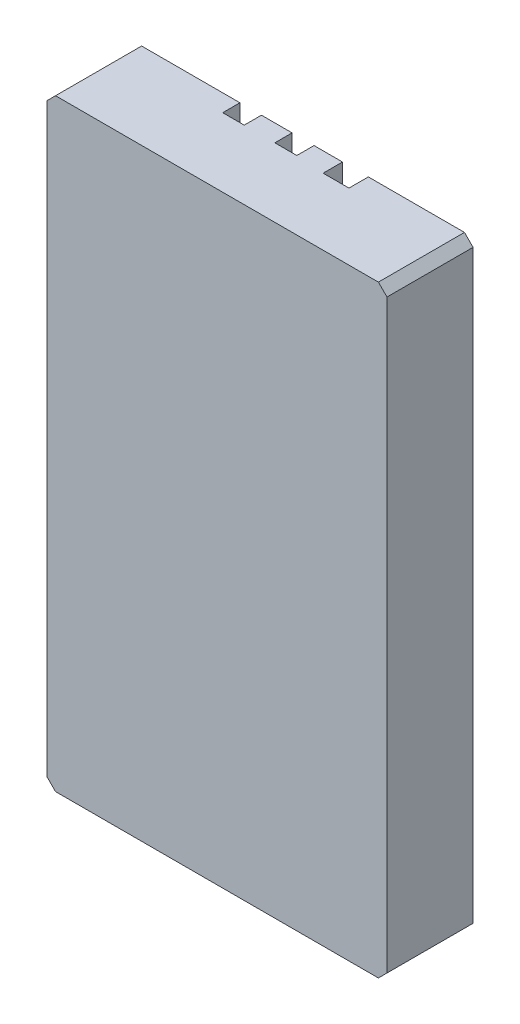
SolidWorks part; units mm, degrees
ref_plane "Front Plane" through (0, 0, 0) normal (0, 0, 1) x (1, 0, 0)
ref_plane "Top Plane" through (0, 0, 0) normal (0, 1, 0) x (1, 0, 0)
ref_plane "Right Plane" through (0, 0, 0) normal (1, 0, 0) x (0, 0, -1)
sketch "Sketch1" plane through (0, 0, 0) normal (0, 0, 1) x (1, 0, 0)
  line L0 (-59.5, -49) -> (17.5, -49) construction
  line L1 (-60.5, -59) -> (18.5, -59)
  line L2 (-60.5, -59) -> (-60.5, -199)
  line L3 (-60.5, -199) -> (18.5, -199)
  line L4 (18.5, -59) -> (18.5, -199)
  dimension "D1" = 79
  dimension "D2" = 140
  dimension "D3" = 10
extrude "Boss-Extrude1" add sketch "Sketch1" against normal blind 20
sketch "Sketch3" plane through (0, -59, 0) normal (0, 1, 0) x (1, 0, 0)
  line L1 (-35.665, 21) -> (-30.665, 21)
  line L2 (-35.665, 21) -> (-35.665, 16)
  line L3 (-35.665, 16) -> (-30.665, 16)
  line L4 (-30.665, 21) -> (-30.665, 16)
  line L5 (-35.665, 21) -> (-30.665, 16) construction
  line L6 (-35.665, 16) -> (-30.665, 21) construction
  point P0 (-33.165, 18.5)
  dimension "D1" = 5
  dimension "D2" = 5
extrude "Cut-Extrude1" cut sketch "Sketch3" against normal blind 131
sketch "Sketch4" plane through (0, 0, -20) normal (0, 0, -1) x (-1, 0, 0)
  line L0 (35.665, -59) -> (35.665, -190) construction
  line L3 (27.665, -190) -> (38.665, -190)
  line L4 (27.665, -190) -> (27.665, -165)
  line L5 (27.665, -165) -> (38.665, -165)
  line L6 (38.665, -190) -> (38.665, -165)
  line L7 (30.665, -190) -> (30.665, -59) construction
  dimension "D1" = 25
  dimension "D2" = 3
  dimension "D3" = 3
extrude "Cut-Extrude2" cut sketch "Sketch4" against normal up to surface (4 mm away) up to face at (-33.165, -124.5, -16)
fillet "Fillet1" radius 2 4 edges at (-27.665, -165, -18) (-27.665, -190, -18) (-38.665, -190, -18) (-38.665, -165, -18)
chamfer "Chamfer1" distance 0.5 angle 45 2 edges at (-30.665, -165, -18) (-35.665, -165, -18)
sketch "Sketch6" plane through (0, -59, 0) normal (0, 1, 0) x (1, 0, 0)
  line L0 (-35.665, 16) -> (-30.665, 16) construction
  line L1 (-23.551, 21) -> (-18.4457, 21)
  line L2 (-23.551, 21) -> (-23.551, 16)
  line L3 (-23.551, 16) -> (-18.4457, 16)
  line L4 (-18.4457, 21) -> (-18.4457, 16)
  line L5 (-23.551, 21) -> (-18.4457, 16) construction
  line L6 (-23.551, 16) -> (-18.4457, 21) construction
  point P0 (-20.9983, 18.5)
  dimension "D1" = 0
  dimension "D2" = 5
extrude "Cut-Extrude3" cut sketch "Sketch6" against normal blind 100
sketch "Sketch7" plane through (0, 0, -20) normal (0, 0, -1) x (-1, 0, 0)
  line L0 (18.4457, -159) -> (18.4457, -59) construction
  line L1 (15.9457, -159) -> (26.051, -159)
  line L2 (15.9457, -159) -> (15.9457, -134)
  line L3 (15.9457, -134) -> (26.051, -134)
  line L4 (26.051, -159) -> (26.051, -134)
  line L5 (23.551, -59) -> (23.551, -159) construction
  dimension "D1" = 25
  dimension "D2" = 2.5
  dimension "D3" = 2.5
extrude "Cut-Extrude4" cut sketch "Sketch7" against normal up to surface (4 mm away) up to face at (-20.9983, -109, -16)
fillet "Fillet2" radius 2 4 edges at (-15.9457, -134, -18) (-15.9457, -159, -18) (-26.051, -159, -18) (-26.051, -134, -18)
chamfer "Chamfer2" distance 0.5 angle 45 2 edges at (-23.551, -134, -18) (-18.4457, -134, -18)
sketch "Sketch8" plane through (0, -59, 0) normal (0, 1, 0) x (1, 0, 0)
  line L1 (-11.8333, 21.5) -> (-5.8333, 21.5)
  line L2 (-11.8333, 21.5) -> (-11.8333, 15.5)
  line L3 (-11.8333, 15.5) -> (-5.8333, 15.5)
  line L4 (-5.8333, 21.5) -> (-5.8333, 15.5)
  line L5 (-11.8333, 21.5) -> (-5.8333, 15.5) construction
  line L6 (-11.8333, 15.5) -> (-5.8333, 21.5) construction
  point P0 (-8.8333, 18.5)
  dimension "D1" = 6
  dimension "D2" = 6
extrude "Cut-Extrude5" cut sketch "Sketch8" against normal blind 103
sketch "Sketch9" plane through (0, 0, -20) normal (0, 0, -1) x (-1, 0, 0)
  line L0 (11.8333, -59) -> (11.8333, -162) construction
  line L1 (3.3333, -162) -> (14.3333, -162)
  line L2 (3.3333, -162) -> (3.3333, -137)
  line L3 (3.3333, -137) -> (14.3333, -137)
  line L4 (14.3333, -162) -> (14.3333, -137)
  line L5 (5.8333, -162) -> (5.8333, -59) construction
  dimension "D1" = 2.5
  dimension "D2" = 2.5
  dimension "D3" = 25
extrude "Cut-Extrude6" cut sketch "Sketch9" against normal up to surface (4.5 mm away) up to face at (-8.8333, -110.5, -15.5)
fillet "Fillet3" radius 2 4 edges at (-3.3333, -137, -17.75) (-3.3333, -162, -17.75) (-14.3333, -162, -17.75) (-14.3333, -137, -17.75)
chamfer "Chamfer3" distance 2 angle 45 4 edges at (-60.5, -59, -10) (18.5, -59, -10) (-60.5, -199, -10) (18.5, -199, -10)
